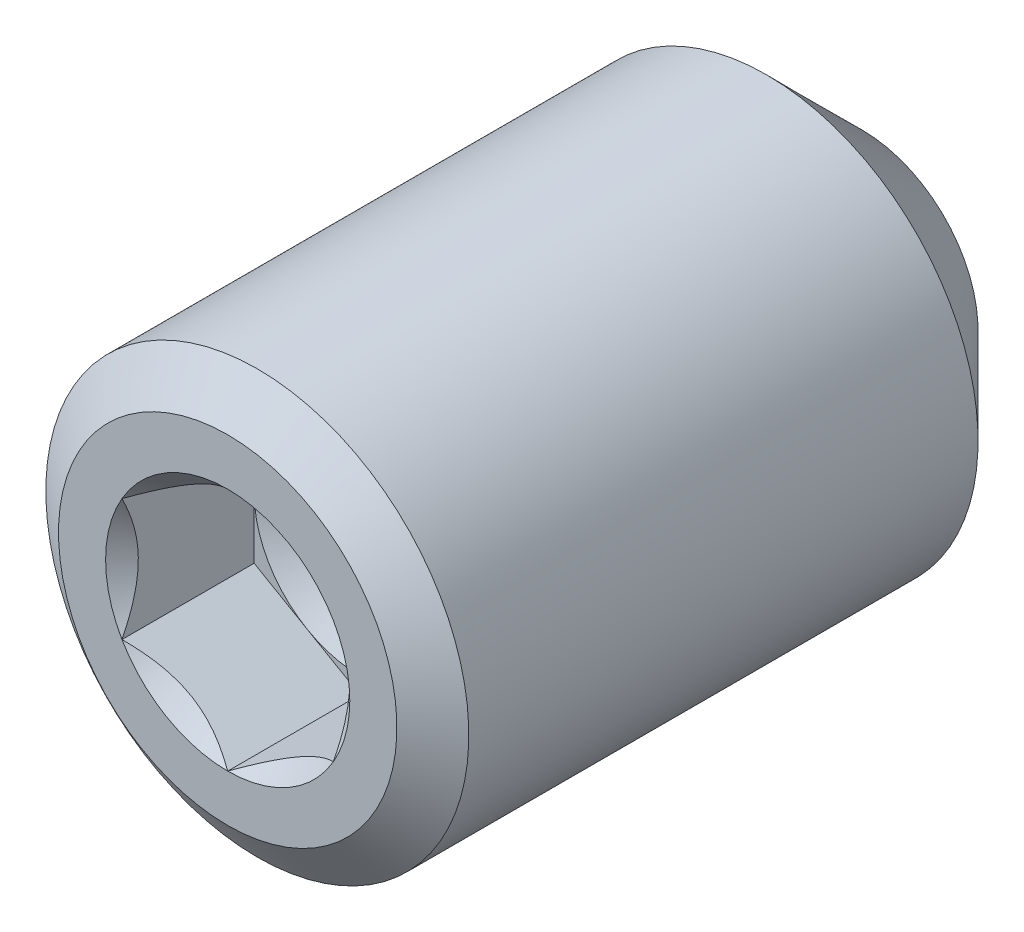
SolidWorks part; units mm, degrees
ref_plane "Front" through (0, 0, 0) normal (0, 0, 1) x (1, 0, 0)
ref_plane "Top" through (0, 0, 0) normal (0, 1, 0) x (1, 0, 0)
ref_plane "Right" through (0, 0, 0) normal (1, 0, 0) x (0, 0, -1)
sketch "Sketch22" plane through (0, 0, 0) normal (1, 0, 0) x (0, 0, -1)
  line L0 (-4.2398, 0) -> (-4.2398, 2.54)
  line L1 (-4.2398, 2.54) -> (-3.7952, 3.175)
  line L2 (-3.7952, 3.175) -> (3.85, 3.175)
  line L3 (3.85, 3.175) -> (5.2852, 1.7398)
  line L4 (5.2852, 1.7398) -> (4.2398, 0)
  line L5 (4.2398, 0) -> (-4.2398, 0)
  line L6 (4.2398, 0) -> (5.2852, 0) construction
  line L7 (5.2852, 0) -> (5.2852, 1.7398) construction
  line L8 (5.2852, -1.7398) -> (4.2398, 0) construction
  line L9 (-3.7952, -3.175) -> (3.85, -3.175) construction
  dimension "Dia" = 6.35
  dimension "Length" = 9.525
  dimension "D3" = 35
  dimension "D5" = 118
  dimension "D6" = 45
  dimension "D7" = 5.08
revolve "Revolve1" add sketch "Sketch22" angle 360 about L6 other way angle 360
ref_plane "Plane1" through (0, 0, -5.2852) normal (0, 0, 1) x (1, 0, 0)
sketch "Sketch27" plane through (0, 0, -5.2852) normal (0, 0, 1) x (1, 0, 0)
  circle A0 centre (0, 0) radius 3.175 construction
  circle A1 centre (0, 0) radius 3.175
curve "Helix/Spiral1" pitch 1.27 height 10.795 turns 8.5
sketch "Sketch28" plane through (0, 0, 0) normal (1, 0, 0) x (0, 0, -1)
  line L0 (5.2852, 3.175) -> (6.3964, 3.175)
  line L1 (6.3964, 3.175) -> (5.9202, 2.3501)
  line L2 (5.9202, 2.3501) -> (5.7614, 2.3501)
  line L3 (5.7614, 2.3501) -> (5.2852, 3.175)
  line L4 (5.5233, 2.7626) -> (6.1583, 2.7626) construction
  line L6 (-3.7952, 3.175) -> (3.85, 3.175) construction
  line L7 (5.2852, 3.4925) -> (5.2852, -3.4925) construction
  dimension "D1" = 0.1588
  dimension "D3" = 60
  dimension "D2" = 0.635
sweep "Cut-Sweep2" [suppressed] cut profiles "Sketch28" path "Helix/Spiral1"
sketch "Sketch23" plane through (0, 0, 4.2398) normal (0, 0, 1) x (1, 0, 0)
  line L1 (0, 1.8331) -> (-1.5875, 0.9165)
  line L2 (-1.5875, 0.9165) -> (-1.5875, -0.9165)
  line L3 (-1.5875, -0.9165) -> (0, -1.8331)
  line L4 (0, -1.8331) -> (1.5875, -0.9165)
  line L5 (1.5875, -0.9165) -> (1.5875, 0.9165)
  line L6 (1.5875, 0.9165) -> (0, 1.8331)
  circle A0 centre (0, 0) radius 1.5875 construction
  dimension "Hex" = 3.175
extrude "Cut-Extrude10" cut sketch "Sketch23" against normal blind 1.9844
sketch "Sketch24" plane through (0, 0, 4.2398) normal (0, 0, 1) x (1, 0, 0)
  circle A0 centre (0, 0) radius 1.8331
extrude "Cut-Extrude11" cut sketch "Sketch24" against normal through all draft 45
sketch "Sketch26" plane through (0, 0, 2.2554) normal (0, 0, 1) x (1, 0, 0)
  circle A0 centre (0, 0) radius 1.5875 construction
  circle A1 centre (0, 0) radius 1.5875
extrude "Cut-Extrude12" cut sketch "Sketch26" against normal through all draft 60
sketch "Sketch30" [suppressed] plane through (0, 0, 0) normal (1, 0, 0) x (0, 0, -1)
  line L0 (-3.7952, 3.175) -> (3.85, 3.175) construction
  line L1 (-4.2398, 0) -> (-4.2398, 2.54) construction
  line L2 (5.2852, 0) -> (5.2852, 1.7398) construction
  line L3 (-3.7952, -3.175) -> (3.85, -3.175) construction
  point P0 (-4.2398, 3.175)
  point P1 (5.2852, 3.175)
  point P2 (5.2852, -3.175)
  point P11 (2.1102, -3.175)
  dimension "D1" = 3.175
sketch "Sketch31" [suppressed] plane through (0, 0, 0) normal (1, 0, 0) x (0, 0, -1)
  line L2 (4.2398, 0) -> (5.2852, -1.7398)
  line L3 (5.2852, 1.7398) -> (4.2398, 0)
equation "\"D7@Sketch22\"=\"Dia@Sketch22\"*.8"
equation "\"D1@Sketch28\" = \"D4@Helix/Spiral1\" * .125"
equation "\"D3@Helix/Spiral1\" = \"Length@Sketch22\" + \"D4@Helix/Spiral1\""
equation "\"D1@Sketch30\" = \"D4@Helix/Spiral1\" * 2.5"
equation "\"hex Depth@Cut-Extrude10\" = \"Hex@Sketch23\" * .625"
equation "\"D2@Sketch28\" = \"D4@Helix/Spiral1\" * .5"
